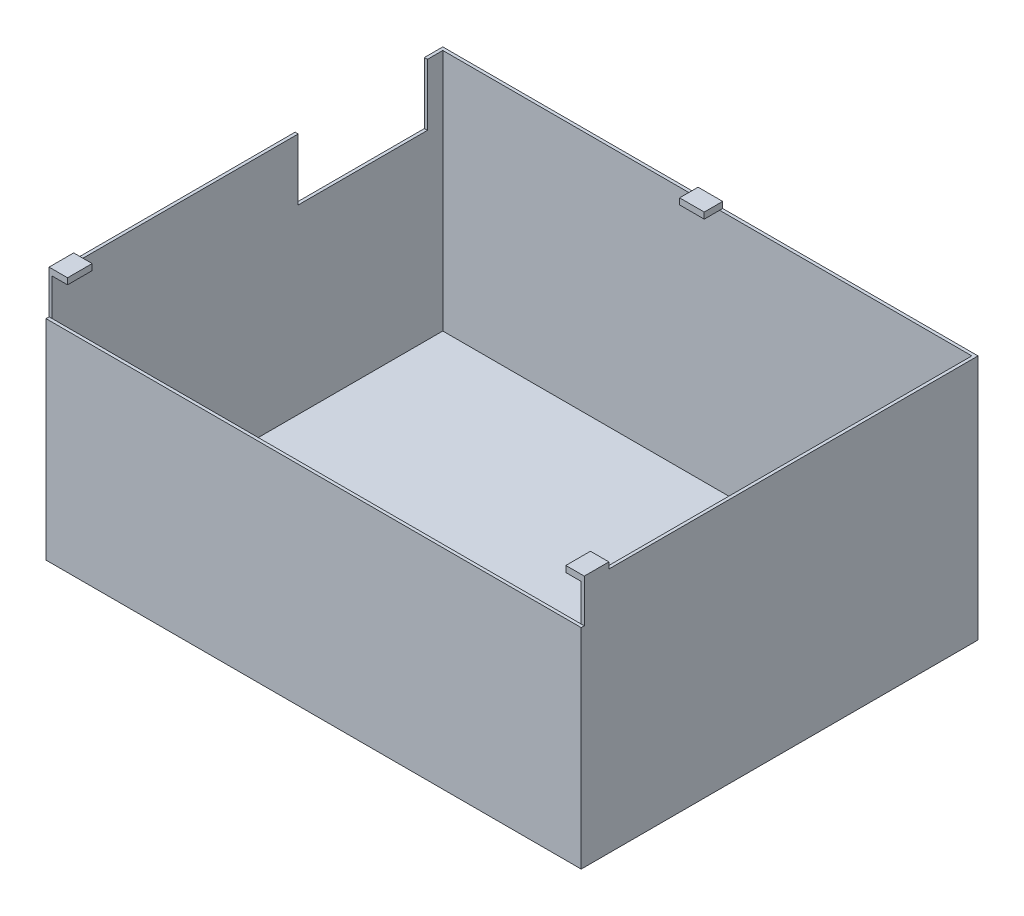
SolidWorks part; units mm, degrees
ref_plane "Front Plane" through (0, 0, 0) normal (0, 0, 1) x (1, 0, 0)
ref_plane "Top Plane" through (0, 0, 0) normal (0, 1, 0) x (1, 0, 0)
ref_plane "Right Plane" through (0, 0, 0) normal (1, 0, 0) x (0, 0, -1)
sketch "Sketch1" plane through (0, 0, 0) normal (0, 1, 0) x (1, 0, 0)
  line L0 (-1, -1) -> (-1, 128)
  line L1 (0, 0) -> (172, 0)
  line L2 (0, 0) -> (0, 127)
  line L3 (0, 127) -> (172, 127)
  line L4 (172, 0) -> (172, 127)
  line L5 (-1, 128) -> (173, 128)
  line L6 (173, -1) -> (173, 128)
  line L7 (-1, -1) -> (173, -1)
  line L8 (0, 0) -> (-1, 0)
  line L9 (172, 0) -> (173, 0)
  dimension "D1" = 172
  dimension "D2" = 127
  dimension "D3" = 1
extrude "Boss-Extrude1" add sketch "Sketch1" along normal blind 1 contours L1 L4 L3 L2 region at (86, 0, -63.5)
extrude "Boss-Extrude2" add sketch "Sketch1<3>" along normal blind 80 contours L4 L9 L6 L5 L0 L8 L2 L3 region at (-0.784, 0, -64)
sketch "Sketch1<3>" plane through (0, 0, 0) normal (0, 1, 0) x (1, 0, 0) same geometry as "Sketch1"
extrude "Boss-Extrude3" add sketch "Sketch1<4>" along normal blind 68 contours L9 L1 L8 L0 L7 L6 region at (86, 0, 0.5)
sketch "Sketch1<4>" plane through (0, 0, 0) normal (0, 1, 0) x (1, 0, 0) same geometry as "Sketch1"
sketch "Sketch4" plane through (0, 80, 0) normal (0, 1, 0) x (1, 0, 0)
  line L0 (-1, 128) -> (173, 128) construction
  line L1 (-1, 0) -> (5, 0)
  line L2 (-1, 0) -> (-1, 8)
  line L3 (-1, 8) -> (5, 8)
  line L4 (5, 0) -> (5, 8)
  line L5 (173, 0) -> (167, 0)
  line L6 (173, 0) -> (173, 8)
  line L7 (173, 8) -> (167, 8)
  line L8 (167, 0) -> (167, 8)
  line L9 (82, 128) -> (90, 128)
  line L10 (82, 128) -> (82, 122)
  line L11 (82, 122) -> (90, 122)
  line L12 (90, 128) -> (90, 122)
  point P16 (86, 128)
  point P17 (86, 128)
  dimension "D1" = 8
  dimension "D2" = 6
  dimension "D3" = 8
  dimension "D5" = 8
extrude "Boss-Extrude4" add sketch "Sketch4" along normal blind 2
sketch "Sketch5" plane through (-1, 0, 0) normal (-1, 0, 0) x (0, 0, 1)
  line L0 (-8, 80) -> (-128, 80) construction
  line L1 (-122, 80) -> (-80, 80)
  line L2 (-122, 80) -> (-122, 60)
  line L3 (-122, 60) -> (-80, 60)
  line L4 (-80, 80) -> (-80, 60)
  line L5 (-128, 80) -> (-128, 0) construction
  dimension "D1" = 6
  dimension "D2" = 20
  dimension "D3" = 42
extrude "Cut-Extrude1" cut sketch "Sketch5" against normal blind 10
